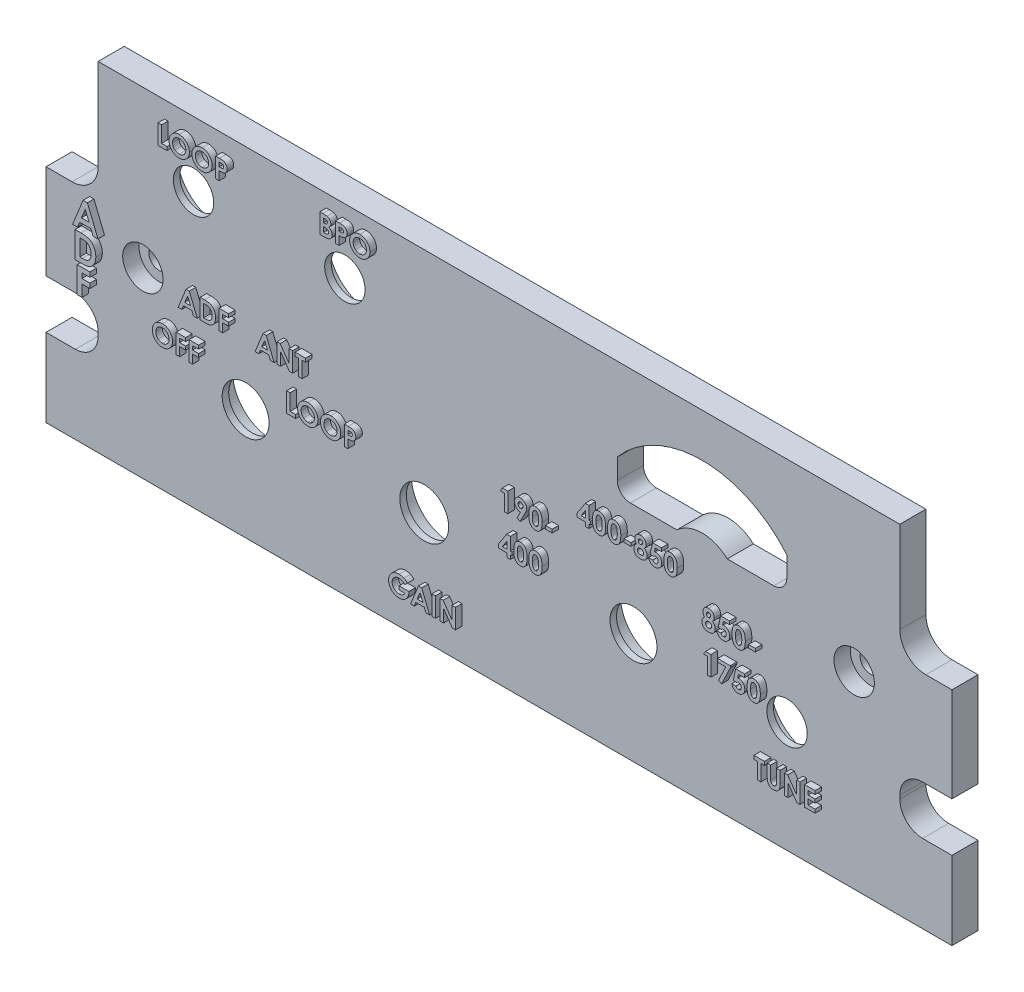
SolidWorks part; units mm, degrees
ref_plane "Front Plane" through (0, 0, 0) normal (0, 0, 1) x (1, 0, 0)
ref_plane "Top Plane" through (0, 0, 0) normal (0, 1, 0) x (1, 0, 0)
ref_plane "Right Plane" through (0, 0, 0) normal (1, 0, 0) x (0, 0, -1)
sketch "Sketch1" plane through (0, 0, 0) normal (0, 0, 1) x (1, 0, 0)
  line L1 (0, 0) -> (139, 0)
  line L2 (0, 0) -> (0, 12)
  line L3 (8, 52) -> (131, 52)
  line L4 (139, 0) -> (139, 12)
  line L5 (69.5, 52) -> (69.5, 0) construction
  line L6 (8, 52) -> (8, 0) construction
  line L11 (131, 52) -> (131, 0) construction
  line L21 (0, 19) -> (139, 19) construction
  line L22 (0, 0) -> (139, 0) construction
  line L23 (0, 0) -> (0, 12) construction
  line L25 (0, 52) -> (0, 64.6609) construction
  line L26 (8, 52) -> (8, 38)
  line L28 (0, 34) -> (4, 34)
  line L29 (8, 15.5) -> (8, 16)
  line L30 (4.5, 19.5) -> (0, 19.5)
  line L31 (0, 12) -> (4.5, 12)
  line L32 (0, 19.5) -> (0, 34)
  line L33 (0, 19.5) -> (0, 34) construction
  line L34 (139, 12) -> (134.5, 12)
  line L35 (134.5, 19.5) -> (139, 19.5)
  line L36 (131, 52) -> (131, 38)
  line L37 (139, 34) -> (135, 34)
  line L38 (139, 19.5) -> (139, 34)
  line L39 (131, 16) -> (131, 15.5)
  line L40 (104.5248, 34.1516) -> (111.6615, 34.1516)
  line L42 (87.6615, 39.2676) -> (87.6615, 36.1516)
  line L43 (89.6615, 34.1516) -> (96.7983, 34.1516)
  line L44 (113.6615, 39.2676) -> (113.6615, 36.1516)
  circle A14 centre (135, 16) radius 1.6 construction
  circle A15 centre (135, 38) radius 1.6 construction
  circle A16 centre (4, 16) radius 1.6 construction
  circle A17 centre (4, 38) radius 1.6 construction
  circle A18 centre (135, 16) radius 1.6 construction
  circle A19 centre (135, 38) radius 1.6 construction
  circle A26 centre (14.8661, 28) radius 1.6 construction
  circle A27 centre (124, 28.9229) radius 1.6 construction
  circle A28 centre (113.7029, 17.0439) radius 3.1 construction
  arc A29 (92.2029, 14.0939) -> (92.2029, 19.9939) centre (90.1395, 17.0439) ccw construction
  circle A30 centre (58.032, 17.0439) radius 3.75 construction
  arc A31 (32.6917, 14.0939) -> (32.6917, 19.9939) centre (30.6284, 17.0439) ccw construction
  circle A32 centre (45.8575, 42.1214) radius 3.1 construction
  circle A33 centre (22.6344, 42.0476) radius 3.1 construction
  circle A34 centre (14.8661, 28) radius 1.6
  circle A35 centre (124, 28.9229) radius 1.6
  circle A46 centre (4, 16) radius 1.6 construction
  circle A47 centre (4, 38) radius 1.6 construction
  arc A49 (8, 38) -> (4, 34) centre (4, 38) cw
  arc A50 (8, 16) -> (4.5, 19.5) centre (4.5, 16) ccw
  arc A51 (4.5, 12) -> (8, 15.5) centre (4.5, 15.5) ccw
  arc A52 (134.5, 12) -> (131, 15.5) centre (134.5, 15.5) cw
  arc A53 (131, 16) -> (134.5, 19.5) centre (134.5, 16) cw
  arc A54 (131, 38) -> (135, 34) centre (135, 38) ccw
  circle A55 centre (113.7029, 17.0439) radius 3.1
  circle A56 centre (90.1395, 17.0439) radius 3.6
  circle A57 centre (58.032, 17.0439) radius 3.75
  circle A58 centre (30.6284, 17.0439) radius 3.6
  circle A59 centre (45.8575, 42.1214) radius 3.1
  circle A60 centre (22.6344, 42.0476) radius 3.1
  arc A63 (111.6615, 34.1516) -> (113.6615, 36.1516) centre (111.6615, 36.1516) ccw
  arc A64 (87.6615, 36.1516) -> (89.6615, 34.1516) centre (89.6615, 36.1516) ccw
  arc A65 (96.7983, 34.1516) -> (104.5248, 34.1516) centre (100.6615, 29.9904) cw
  arc A66 (87.6615, 39.2676) -> (113.6615, 39.2676) centre (100.6615, 28.389) cw
  point P22 (8, 34)
  point P67 (8, 19.5)
  dimension "D3" = 139
  dimension "D4" = 8
  dimension "D5" = 18
  dimension "D8" = 4
  dimension "D12" = 22
  dimension "D6" = 4
  dimension "D10" = 3.5
  dimension "D11" = 3.5
  dimension "D14" = 2
  dimension "D1" = 123
  dimension "D7" = 3.5
  dimension "D20" = 52
  dimension "D9" = 4
extrude "Extrusion base" add sketch "Sketch1" along normal blind 4
sketch "Sketch6" plane through (0, 0, 0) normal (0, 0, -1) x (-1, 0, 0)
  circle A0 centre (-113.7029, 17.0439) radius 6.6
  circle A1 centre (-90.1395, 17.0439) radius 6
  circle A2 centre (-58.032, 17.0439) radius 6
  circle A3 centre (-30.6284, 17.0439) radius 6
  circle A4 centre (-22.6344, 42.0476) radius 6.6
  circle A5 centre (-45.8575, 42.1214) radius 6.6
  dimension "D1" = 13.2
  dimension "D2" = 12
  dimension "D3" = 12
  dimension "D4" = 12
extrude "Back Holes" cut sketch "Sketch6" against normal blind 3
sketch "Sketch4" plane through (0, 0, 4) normal (0, 0, 1) x (1, 0, 0)
  line L0 (8, 26.9631) -> (8, 14.5758) construction
  line L3 (-3.8412, 29.3922) -> (13.9628, 29.3922) construction
  line L4 (-4.2039, 24.8922) -> (13.9628, 24.8922) construction
  line L5 (-4.2039, 20.3922) -> (14.2039, 20.3922) construction
  line L6 (5, 33.1522) -> (5, -6.1206) construction
  text T0 "<b>A</b>" font "Century Gothic" height 4
  text T1 "<b>ADF</b>\r\n" font "Century Gothic" height 3
  text T2 "<b>ANT</b>" font "Century Gothic" height 3
  text T3 "<b>LOOP</b>" font "Century Gothic" height 3
  text T4 "<b>OFF</b>" font "Century Gothic" height 3
  text T5 "<b>190-</b>\r\n<b>400</b>" font "Century Gothic" height 3
  text T6 "<b>TUNE</b>" font "Century Gothic" height 3
  text T7 "D" font "Century Gothic" height 4
  text T8 "F" font "Century Gothic" height 4
  text T9 "<b>GAIN</b>" font "Century Gothic" height 3
  text T10 "<b>400-850</b>" font "Century Gothic" height 3
  text T11 "<b>LOOP</b>" font "Century Gothic" height 3
  text T12 "<b>BPO</b>" font "Century Gothic" height 3
  text T13 "<b>850-</b>\r\n<b>1750</b>" font "Century Gothic" height 3
  dimension "D1" = 4.5
  dimension "D2" = 4.5
  dimension "D3" = 3
extrude "Textos" add sketch "Sketch4" along normal blind 1
sketch "Sketch7" plane through (0, 0, 4) normal (0, 0, 1) x (1, 0, 0)
  circle A1 centre (124, 28.9229) radius 3.1
  circle A2 centre (14.8661, 28) radius 3.1
  circle A3 centre (124, 28.9229) radius 1.6 construction
  dimension "D1" = 1.5
extrude "Cut-Extrude2" cut sketch "Sketch7" against normal blind 2.5
